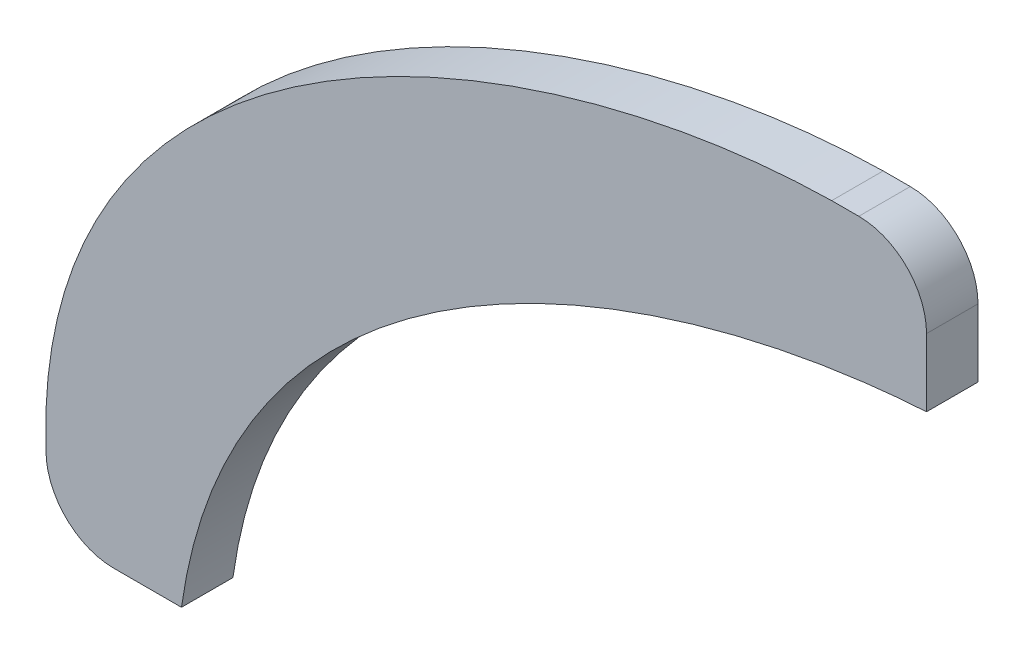
SolidWorks part; units mm, degrees
ref_plane "Front Plane" through (0, 0, 0) normal (0, 0, 1) x (1, 0, 0)
ref_plane "Top Plane" through (0, 0, 0) normal (0, 1, 0) x (1, 0, 0)
ref_plane "Right Plane" through (0, 0, 0) normal (1, 0, 0) x (0, 0, -1)
sketch "Sketch1" plane through (0, 0, 0) normal (0, 0, 1) x (1, 0, 0)
  line L1 (6.35, 0) -> (82.55, 0)
  line L2 (0, 6.35) -> (0, 63.5)
  line L3 (0, 63.5) -> (76.2, 63.5)
  line L4 (82.55, 0) -> (82.55, 57.15)
  arc A0 (82.55, 57.15) -> (76.2, 63.5) centre (76.2, 57.15) ccw
  arc A1 (0, 6.35) -> (6.35, 0) centre (6.35, 6.35) ccw
  spline S0 degree 3 poles (0, 6.35) (-1.4343, 43.9963) (45.0346, 64.052) (76.2, 63.5) knots 0 0 0 0 1 1 1 1
  spline S1 degree 3 poles (12.7, 0) (17.2635, 32.9464) (53.3334, 49.0332) (82.55, 50.8) knots 0 0 0 0 1 1 1 1
  point P7 (82.55, 63.5)
  point P10 (0, 0)
  dimension "D3" = 6.35
  dimension "D4" = 12.7
  dimension "D1" = 82.55
  dimension "D2" = 63.5
  dimension "D5" = 12.7
extrude "Boss-Extrude1" add sketch "Sketch1" along normal blind 4.826 contours L1 S1 L4 A0 L3 S0 L2 A1 region at (34.6367, 38.2503, 0)
equation "\"MDF\"= 0.19in"
equation "\"PVCID\" = 2.067in"
equation "\"PVCOD\" = 2.375in"
equation "\"GenDiameter\"= 60mm"
equation "\"GenCutDiameter\" = 1.8in"
equation "\"GenCutDistance\" = 1"
equation "\"TowerHeight\" = 6in"
equation "\"TowerFrontBase\" = 3in"
equation "\"FunnelHeight\" = 1in"
equation "\"FunnelAngle\" = 20"
equation "\"TowerSideBase\" = 3in"
equation "\"TowerPanelLength\" = 2in"
equation "\"TowerPanelLeeway\" = 0.5in"
equation "\"BaseLength\" = 9in"
equation "\"BaseWidth\" = 10in"
equation "\"WheelHoleLength\" = 3.25in"
equation "\"WheelHoleWidth\" = 26mm"
equation "\"WheelHoleFromBack\" = 1.5in"
equation "\"DropLength\" = 1in"
equation "\"DropWidth\" = 8.5in"
equation "\"BumperWidth\" = 2in"
equation "\"SmallHexDiameter\" = 0.185in"
equation "\"SmallHexHeight\" = 0.701in"
equation "\"ScrewSize\" = 0.106in"
equation "\"BigHexDiameter\" = 0.251in"
equation "\"BigHexHeight\" = 0.374in"
equation "\"PCBThickness\" = 0.066in"
equation "\"ConnectorHeight\" = 0.517in"
equation "\"BoardHeight\" = 0.583in"
equation "\"UnoStackHeight\" = 1.351in"
equation "\"UnoStackWidth\" = 3.053in"
equation "\"UnoStackLength\" = 3.152in"
equation "\"HBridgeWidth\" = 1.797in"
equation "\"HBridgeLength\" = 2.236in"
equation "\"DSWidth\" = 1.820in"
equation "\"DSLength\" = 1.833in"
equation "\"StepperWidth\" = 1.799in"
equation "\"StepperLength\" = 2.248in"
equation "\"ULNWidth\" = 1.304in"
equation "\"ULNLength\" = 1.545in"
equation "\"VSwitchHeight\" = 0.392in"
equation "\"VSwitchWidth\" = 0.637in"
equation "\"VSwitchLength\" = 1.097in"
equation "\"SkateWheelDiameter\" = 80mm"
equation "\"SkateWheelThickness\" = 24mm"
equation "\"BaseDistance\" = 3in"
equation "\"DummyVar\" = 2in"
equation "\"D1@Boss-Extrude1\"=\"MDF\""
